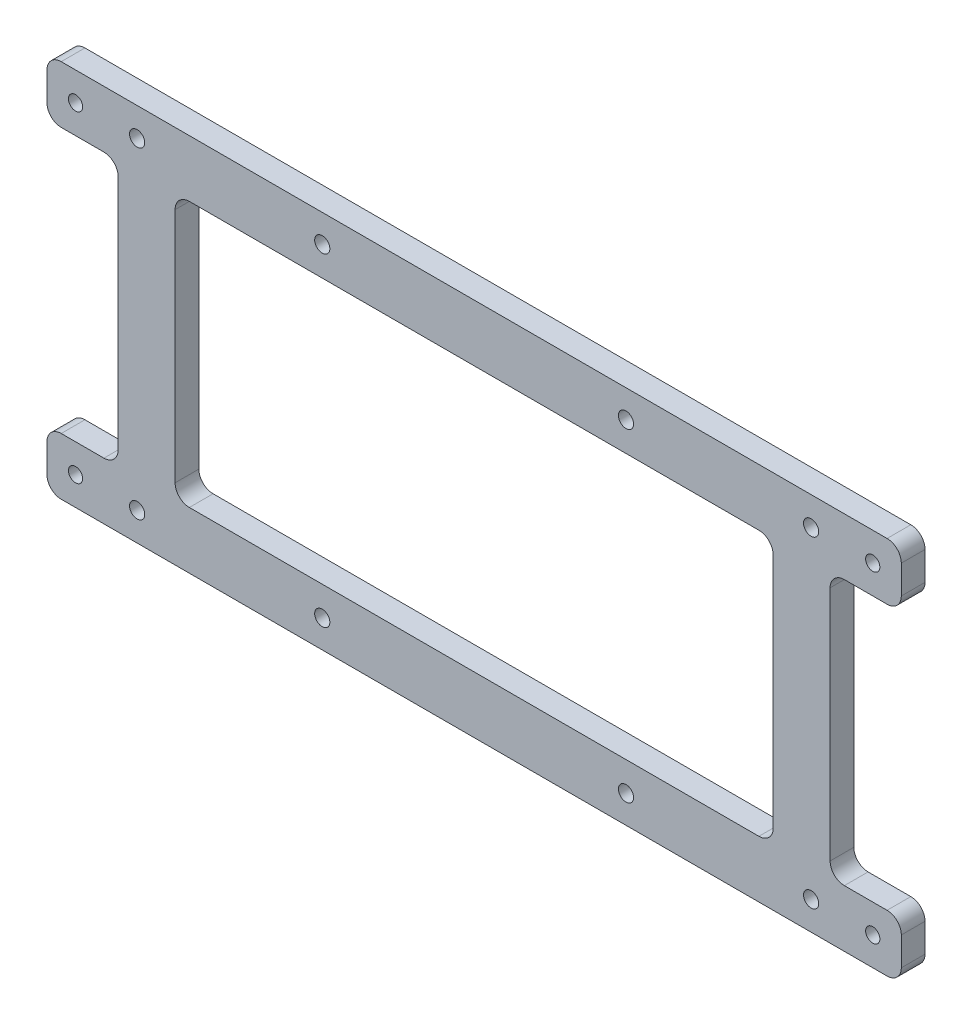
SolidWorks part; units mm, degrees
ref_plane "前视基准面" through (0, 0, 0) normal (0, 0, 1) x (1, 0, 0)
ref_plane "上视基准面" through (0, 0, 0) normal (0, 1, 0) x (1, 0, 0)
ref_plane "右视基准面" through (0, 0, 0) normal (1, 0, 0) x (0, 0, -1)
sketch "草图1" plane through (0, 0, 0) normal (0, 0, 1) x (1, 0, 0)
  line L0 (-8, 27.8432) -> (-8, -28)
  line L2 (-8, 40) -> (-8, 39.8432)
  line L4 (142, 40) -> (142, 39.8432)
  line L5 (-20, 39.8432) -> (154, 39.8432)
  line L6 (-23, 36.8432) -> (-23, 30.8432)
  line L7 (-20, 27.8432) -> (-8, 27.8432)
  line L8 (157, 36.8432) -> (157, 30.8432)
  line L9 (-20, -40) -> (154, -40)
  line L10 (-23, -37) -> (-23, -31)
  line L11 (-20, -28) -> (-8, -28)
  line L12 (157, -37) -> (157, -31)
  line L13 (142, 27.8432) -> (154, 27.8432)
  line L14 (142, -28) -> (154, -28)
  line L15 (142, 27.8432) -> (142, -28)
  line L17 (7, 27.8432) -> (127, 27.8432)
  line L18 (4, 24.8432) -> (4, -25)
  line L19 (7, -28) -> (127, -28)
  line L20 (130, 24.8432) -> (130, -25)
  arc A0 (154, -40) -> (157, -37) centre (154, -37) ccw
  arc A1 (154, -28) -> (157, -31) centre (154, -31) cw
  arc A2 (154, 27.8432) -> (157, 30.8432) centre (154, 30.8432) ccw
  arc A3 (154, 39.8432) -> (157, 36.8432) centre (154, 36.8432) cw
  arc A4 (-20, -40) -> (-23, -37) centre (-20, -37) cw
  arc A5 (-23, -31) -> (-20, -28) centre (-20, -31) cw
  arc A6 (-23, 30.8432) -> (-20, 27.8432) centre (-20, 30.8432) ccw
  arc A7 (-20, 39.8432) -> (-23, 36.8432) centre (-20, 36.8432) ccw
  arc A8 (127, -28) -> (130, -25) centre (127, -25) ccw
  arc A9 (127, 27.8432) -> (130, 24.8432) centre (127, 24.8432) cw
  arc A10 (4, -25) -> (7, -28) centre (7, -25) ccw
  arc A11 (7, 27.8432) -> (4, 24.8432) centre (7, 24.8432) ccw
  point P20 (157, -40)
  point P23 (157, -28)
  point P26 (157, 27.8432)
  point P29 (157, 39.8432)
  dimension "D7" = 3
  dimension "D10" = 3
  dimension "D1" = 15
  dimension "D2" = 15
  dimension "D3" = 15
  dimension "D4" = 15
  dimension "D5" = 12
  dimension "D6" = 12
  dimension "D8" = 12
  dimension "D9" = 12
  dimension "D11" = 150
extrude "凸台-拉伸1" add sketch "草图1" along normal blind 5 contours L5 A7 L6 A6 L7 L0 L11 A5 L10 A4 L9 A0 L12 A1 L14 L15 L13 A2 L8 A3 A11 L17 A9 L20 A8 L19 A10 L18 region at (-14, 29.8124, 0)
fillet "圆角1" radius 3 4 edges at (-8, -28, 2.5) (-8, 27.8432, 2.5) (142, -28, 2.5) (142, 27.8432, 2.5)
sketch "草图2" plane through (0, 0, 5) normal (0, 0, 1) x (1, 0, 0)
  line L0 (67, 39.8432) -> (67, -40) construction
  line L1 (-20, 39.8432) -> (154, 39.8432) construction
  line L2 (-20, -40) -> (154, -40) construction
  line L3 (-8, -0.0784) -> (142, -0.0784) construction
  line L4 (-8, 24.8432) -> (-8, -25) construction
  line L5 (142, 24.8432) -> (142, -25) construction
  line L6 (31.0016, 40) -> (39.0016, 40) construction
  line L7 (31.0016, -40) -> (31.0016, 40) construction
  circle A0 centre (-16.978, 33.8432) radius 1.5
  circle A1 centre (-4, 33.8432) radius 1.6
  circle A2 centre (35.0016, 34) radius 1.6
  circle A3 centre (98.9984, 34) radius 1.6
  circle A4 centre (138, 33.8432) radius 1.6
  circle A5 centre (150.978, 33.8432) radius 1.5
  circle A6 centre (150.978, -34) radius 1.5
  circle A7 centre (138, -34) radius 1.6
  circle A8 centre (98.9984, -34.1568) radius 1.6
  circle A9 centre (35.0016, -34.1568) radius 1.6
  circle A10 centre (-4, -34) radius 1.6
  circle A11 centre (-16.978, -34) radius 1.5
  dimension "D1" = 3
  dimension "D2" = 3.2
  dimension "D3" = 3.2
  dimension "D4" = 6
  dimension "D5" = 6
  dimension "D6" = 6
  dimension "D7" = 4
  dimension "D8" = 4
extrude "切除-拉伸1" cut sketch "草图2" against normal blind 7
